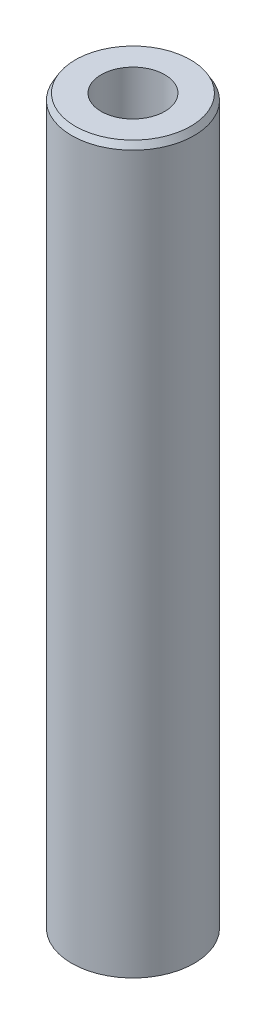
SolidWorks part; units mm, degrees
ref_plane "Front Plane" through (0, 0, 0) normal (0, 0, 1) x (1, 0, 0)
ref_plane "Top Plane" through (0, 0, 0) normal (0, 1, 0) x (1, 0, 0)
ref_plane "Right Plane" through (0, 0, 0) normal (1, 0, 0) x (0, 0, -1)
sketch "Sketch1" plane through (0, 0, 0) normal (0, 1, 0) x (1, 0, 0)
  circle A0 centre (0, 0) radius 42.5
  dimension "SHAFT_OD" = 85
extrude "Boss-Extrude1" add sketch "Sketch1" along normal blind 504.3736
sketch "Sketch2" plane through (0, 0, 0) normal (0, 1, 0) x (1, 0, 0)
  circle A0 centre (0, 0) radius 22.092
  dimension "BORE_D" = 44.1839
extrude "Cut-Extrude1" cut sketch "Sketch2" along normal through all
chamfer "Chamfer1" distance 4.3188 angle 30 2 edges at (0, 504.3736, 42.5) (0, 0, 42.5) first distance on face at (0, 504.3736, 42.5) first distance on face at (0, 0, 22.092)
